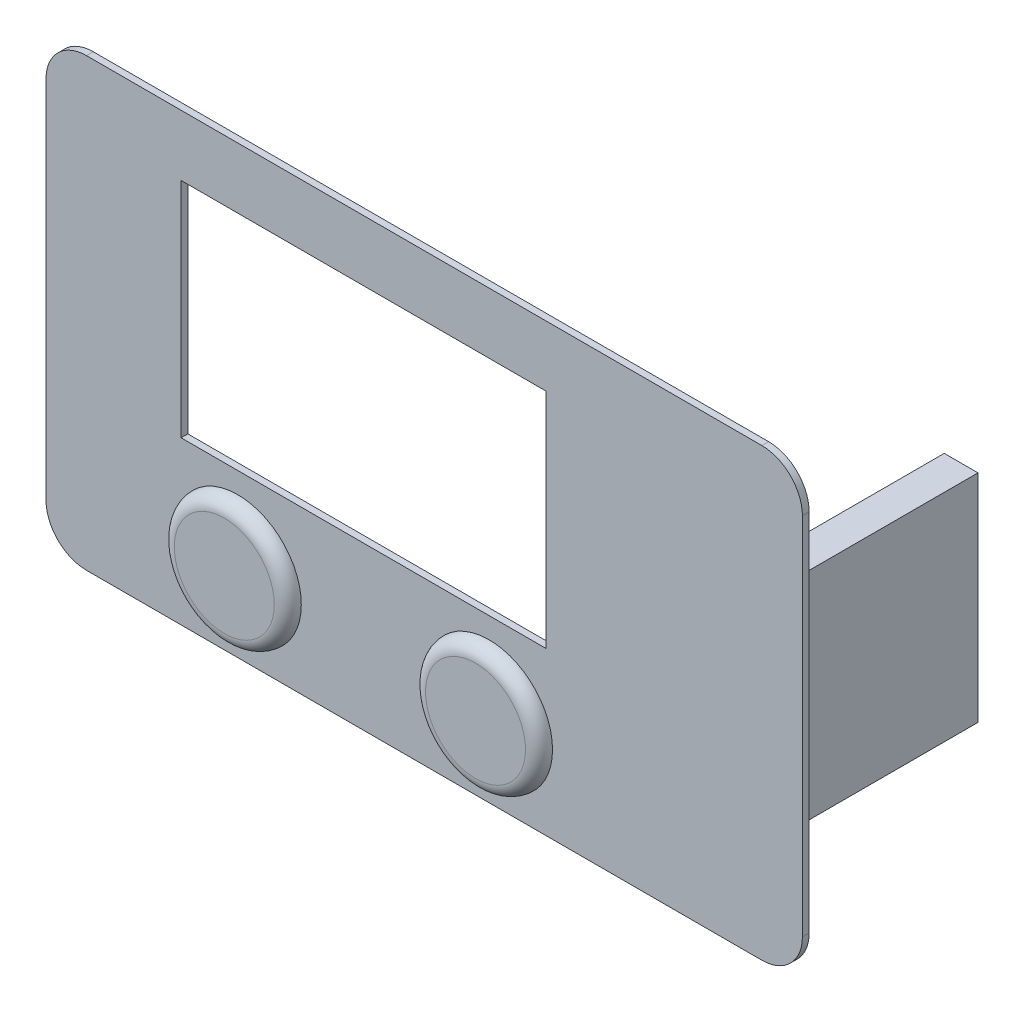
SolidWorks part; units mm, degrees
ref_plane "Front Plane" through (0, 0, 0) normal (0, 0, 1) x (1, 0, 0)
ref_plane "Top Plane" through (0, 0, 0) normal (0, 1, 0) x (1, 0, 0)
ref_plane "Right Plane" through (0, 0, 0) normal (1, 0, 0) x (0, 0, -1)
sketch "Sketch1" plane through (0, 0, 0) normal (0, 0, 1) x (1, 0, 0)
  line L1 (-28, 16.5) -> (28, 16.5)
  line L2 (-28, 16.5) -> (-28, -16.5)
  line L3 (-28, -16.5) -> (28, -16.5)
  line L4 (28, 16.5) -> (28, -16.5)
  line L5 (-28, 16.5) -> (28, -16.5) construction
  line L6 (-28, -16.5) -> (28, 16.5) construction
  point P0 (0, 0)
  dimension "D1" = 56
  dimension "D2" = 33
extrude "Boss-Extrude1" add sketch "Sketch1" along normal blind 0.5
sketch "Sketch2" plane through (0, 0, 0.5) normal (0, 0, 1) x (1, 0, 0)
  line L0 (28, 16.5) -> (-28, 16.5) construction
  line L1 (-18, 12) -> (9, 12)
  line L2 (-18, 12) -> (-18, -4.5)
  line L3 (-18, -4.5) -> (9, -4.5)
  line L4 (9, 12) -> (9, -4.5)
  line L5 (-28, 16.5) -> (-28, -16.5) construction
  dimension "D1" = 27
  dimension "D2" = 16.5
  dimension "D3" = 4.5
  dimension "D4" = 10
extrude "Cut-Extrude1" cut sketch "Sketch2" against normal up to surface (0.5 mm away) up to face at (0, 0, 0)
sketch "Sketch3" plane through (0, 0, 0.5) normal (0, 0, 1) x (1, 0, 0)
  line L0 (-18, -4.5) -> (9, -4.5) construction
  line L2 (-18, 12) -> (-18, -4.5) construction
  line L3 (9, -4.5) -> (9, 12) construction
  circle A0 centre (-13.8, -10.75) radius 4.7
  circle A1 centre (4.8, -10.75) radius 4.7
  dimension "D1" = 9.4
  dimension "D2" = 9.4
  dimension "D4" = 6.25
  dimension "D6" = 4.2
  dimension "D3" = 6.25
  dimension "D5" = 4.2
extrude "Boss-Extrude2" add sketch "Sketch3" along normal blind 1
fillet "Fillet1" radius 1 2 edges at (-9.1, -10.75, 1.5) (9.5, -10.75, 1.5)
sketch "Sketch4" plane through (0, 0, 0) normal (0, 0, -1) x (-1, 0, 0)
  line L0 (-28, -16.5) -> (-28, 16.5) construction
  line L1 (-25.5, 7.25) -> (-23, 7.25)
  line L2 (-25.5, 7.25) -> (-25.5, -8.75)
  line L3 (-25.5, -8.75) -> (-23, -8.75)
  line L4 (-23, 7.25) -> (-23, -8.75)
  line L5 (-28, 16.5) -> (28, 16.5) construction
  line L6 (28, -16.5) -> (-28, -16.5) construction
  dimension "D1" = 2.5
  dimension "D2" = 2.5
  dimension "D3" = 9.25
  dimension "D4" = 7.75
extrude "Boss-Extrude3" add sketch "Sketch4" along normal blind 15
fillet "Fillet2" radius 3 4 edges at (-28, 16.5, 0.25) (-28, -16.5, 0.25) (28, -16.5, 0.25) (28, 16.5, 0.25)
